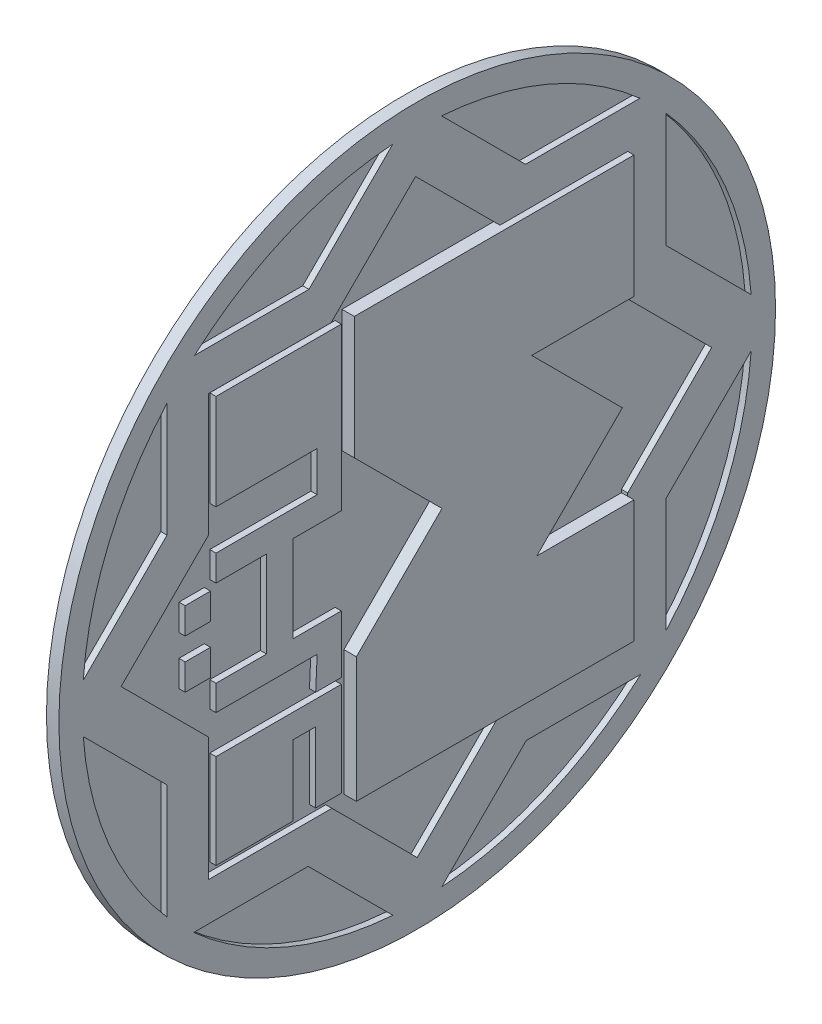
SolidWorks part; units mm, degrees
ref_plane "Front Plane" through (0, 0, 0) normal (1, 0, 0) x (0, 1, 0)
ref_plane "Top Plane" through (0, 0, 0) normal (0, 0, 1) x (0, 1, 0)
ref_plane "Right Plane" through (0, 0, 0) normal (0, 1, 0) x (-1, 0, 0)
sketch "Sketch10" plane through (0, 0, 0) normal (1, 0, 0) x (0, 1, 0)
  line L0 (112.3213, 271.3951) -> (496.9879, 271.3951) construction
sketch "Sketch11" plane through (0, 0, 0) normal (1, 0, 0) x (0, 1, 0)
  line L0 (288.5, 18.9287) -> (288.5, 52.731) construction
  line L1 (0, 0) -> (577, 0)
  line L2 (0, 0) -> (0, 577)
  line L3 (0, 577) -> (577, 577)
  line L4 (577, 0) -> (577, 577)
  line L5 (18.9287, 288.5) -> (50.0746, 288.5) construction
  line L6 (268.8545, 557.3545) -> (201.4256, 489.9256)
  line L7 (109.3453, 489.9256) -> (201.4256, 489.9256)
  line L8 (87.8146, 468.4835) -> (87.8146, 376.3146)
  line L9 (108.0168, 88.2638) -> (200.2362, 88.2638)
  line L10 (489.8357, 467.7558) -> (489.8357, 375.6643)
  line L11 (118.728, 456.3548) -> (217.9294, 456.3548)
  line L12 (118.728, 456.3548) -> (118.728, 357.1534)
  line L13 (118.728, 119.0164) -> (219.5583, 119.0164)
  line L14 (457.6577, 456.3548) -> (457.6577, 357.7677)
  line L15 (308.1455, 557.3545) -> (375.5744, 489.9256)
  line L16 (19.6455, 268.8545) -> (87.8146, 200.6854)
  line L17 (557.3545, 268.8545) -> (489.8357, 201.3357)
  line L18 (288.5, 526.9254) -> (217.9294, 456.3548)
  line L19 (288.5, 526.9254) -> (359.0706, 456.3548)
  line L20 (50.0746, 288.5) -> (118.728, 219.8466)
  line L21 (525.5972, 289.8282) -> (457.6577, 221.8887)
  line L22 (457.6577, 221.8887) -> (457.6577, 119.0164)
  line L23 (118.728, 357.1534) -> (50.0746, 288.5)
  line L24 (375.5744, 489.9256) -> (467.6547, 489.9256)
  line L25 (524.269, 288.5) -> (558.0713, 288.5) construction
  line L26 (489.8357, 375.6643) -> (557.3545, 308.1455)
  line L27 (354.7854, 119.0164) -> (287.1718, 51.4028)
  line L28 (489.8357, 201.3357) -> (489.8357, 109.2442)
  line L29 (354.7854, 119.0164) -> (457.6577, 119.0164)
  line L30 (376.7638, 88.2638) -> (308.1455, 19.6455)
  line L31 (87.8146, 376.3146) -> (19.6455, 308.1455)
  line L32 (87.8146, 200.6854) -> (87.8146, 108.5165)
  line L33 (118.728, 219.8466) -> (118.728, 119.0164)
  line L34 (87.8146, 288.5) -> (489.8357, 288.5) construction
  line L35 (359.0706, 456.3548) -> (457.6577, 456.3548)
  line L36 (457.6577, 357.7677) -> (525.5972, 289.8282)
  line L37 (288.5, 288.5) -> (288.5, 566.8808) construction
  line L38 (376.7638, 88.2638) -> (468.9832, 88.2638)
  line L39 (219.5583, 119.0164) -> (287.1718, 51.4028)
  line L40 (200.2362, 88.2638) -> (268.8545, 19.6455)
  line L41 (577, 288.5) -> (762.5914, 288.5) construction
  line L42 (125.4899, 450.4889) -> (201.4256, 450.4889)
  line L43 (201.4256, 450.4889) -> (201.4256, 349.6326)
  line L44 (201.4256, 349.6326) -> (125.4899, 349.6326)
  line L45 (125.4899, 349.6326) -> (125.4899, 370.2455)
  line L46 (125.4899, 370.2455) -> (182.1756, 370.2455)
  line L47 (182.1756, 370.2455) -> (182.1756, 388.4585)
  line L48 (182.1756, 388.4585) -> (125.4899, 388.4585)
  line L49 (125.4899, 388.4585) -> (125.4899, 450.4889)
  line L50 (206.1638, 370.2455) -> (206.1638, 349.6326)
  line L51 (206.1638, 349.6326) -> (252.5935, 349.6326)
  line L52 (252.5935, 349.6326) -> (252.5935, 388.4585)
  line L53 (252.5935, 388.4585) -> (322.4121, 388.4585)
  line L54 (322.4121, 388.4585) -> (322.4121, 349.6326)
  line L55 (322.4121, 349.6326) -> (452.5889, 349.6326)
  line L56 (452.5889, 349.6326) -> (452.5889, 450.4889)
  line L57 (452.5889, 450.4889) -> (375.5744, 450.4889)
  line L58 (375.5744, 450.4889) -> (375.5744, 369.0455)
  line L59 (375.5744, 369.0455) -> (343.3496, 369.0455)
  line L60 (343.3496, 369.0455) -> (343.3496, 450.4889)
  line L61 (343.3496, 450.4889) -> (322.4121, 450.4889)
  line L62 (322.4121, 450.4889) -> (322.4121, 409.7672)
  line L63 (322.4121, 409.7672) -> (252.5935, 409.7672)
  line L64 (252.5935, 409.7672) -> (252.5935, 450.4889)
  line L65 (252.5935, 450.4889) -> (232.1034, 450.4889)
  line L66 (232.1034, 450.4889) -> (232.1034, 369.0455)
  line L67 (232.1034, 369.0455) -> (206.1638, 370.2455)
  line L68 (258.7348, 475.3138) -> (279.8966, 475.3138)
  line L69 (279.8966, 475.3138) -> (279.8966, 454.9358)
  line L70 (279.8966, 454.9358) -> (258.7348, 454.9358)
  line L71 (258.7348, 454.9358) -> (258.7348, 475.3138)
  line L72 (297.9233, 475.3138) -> (319.0851, 475.3138)
  line L73 (319.0851, 475.3138) -> (319.0851, 454.9358)
  line L74 (319.0851, 454.9358) -> (297.9233, 454.9358)
  line L75 (297.9233, 454.9358) -> (297.9233, 475.3138)
  line L76 (118.728, 342.4907) -> (219.5583, 342.4907)
  line L77 (219.5583, 342.4907) -> (288.5, 273.549)
  line L78 (288.5, 273.549) -> (359.0706, 344.1195)
  line L79 (359.0706, 344.1195) -> (457.6577, 344.1195)
  line L80 (457.6577, 344.1195) -> (457.6577, 119.0164)
  line L81 (359.0706, 119.0164) -> (359.0706, 201.3357)
  line L82 (359.0706, 201.3357) -> (286.078, 128.3431)
  line L83 (286.078, 128.3431) -> (217.2198, 197.2013)
  line L84 (217.2198, 197.2013) -> (217.2198, 119.0164)
  line L85 (118.728, 119.0164) -> (118.728, 342.4907)
  circle A0 centre (288.5, 288.5) radius 288.5
  circle A1 centre (288.5, 288.5) radius 269.5713
  dimension "D1" = 577
  dimension "D2" = 577
extrude "Boss-Extrude7" add sketch "Sketch11" along normal blind 10 contours A0 A1 | L38 A1 L28 L17 L26 L10 L24 L15 L6 L7 L8 L31 L16 L32 L9 L40 L30 L39 L13 L33 L20 L23 L12 L11 L18 L19 L35 L14 L36 L21 L22 L29 L27 | L49 L48 L47 L46 L45 L44 L43 L42 | L66 L67 L50 L51 L52 L53 L54 L55 L56 L57 L58 L59 L60 L61 L62 L63 L64 L65 | L75 L74 L73 L72 | L68 L69 L70 L71 region at (0, 90.2697, 90.2697) region at (0, 288.5, 550.4467) region at (0, 164.9574, 403.2873) region at (0, 219.0105, 366.9857) region at (0, 308.5042, 465.1248)
extrude "Boss-Extrude8" add sketch "Sketch11<7>" along normal blind 5 contours L8 A1 L31 | L6 A1 L7 | L24 A1 L15 | L26 A1 L10 | L28 A1 L17 | L30 A1 L38 | L9 A1 L40 | L16 A1 L32 | L20 L85 L76 L77 L78 L79 L80 L21 L36 L14 L35 L19 L18 L11 L12 L23 L67 L66 L65 L64 L63 L62 L61 L60 L59 L58 L57 L56 L55 L54 L53 L52 L51 L50 L48 L49 L42 L43 L44 L45 L46 L47 L70 L71 L68 L69 L74 | L83 L84 L13 L39 L27 L29 L81 L82 region at (0, 191.0017, 518.1512) region at (0, 385.9983, 518.1512) region at (0, 59.2525, 386.5066) region at (0, 518.1021, 386.0603) region at (0, 59.2525, 190.4934) region at (0, 518.1021, 190.9397) region at (0, 190.1862, 59.4972) region at (0, 386.8138, 59.4972) region at (0, 282.3951, 369.9967) region at (0, 288.6892, 125.3593)
sketch "Sketch11<7>" plane through (0, 0, 0) normal (1, 0, 0) x (0, 1, 0) same geometry as "Sketch11"
extrude "Boss-Extrude9" add sketch "Sketch11<8>" along normal blind 15 contours L85 L33 L13 L84 L83 L82 L81 L29 L22 L80 L79 L78 L77 L76 region at (0, 288.3138, 232.8278)
sketch "Sketch11<8>" plane through (0, 0, 0) normal (1, 0, 0) x (0, 1, 0) same geometry as "Sketch11"
